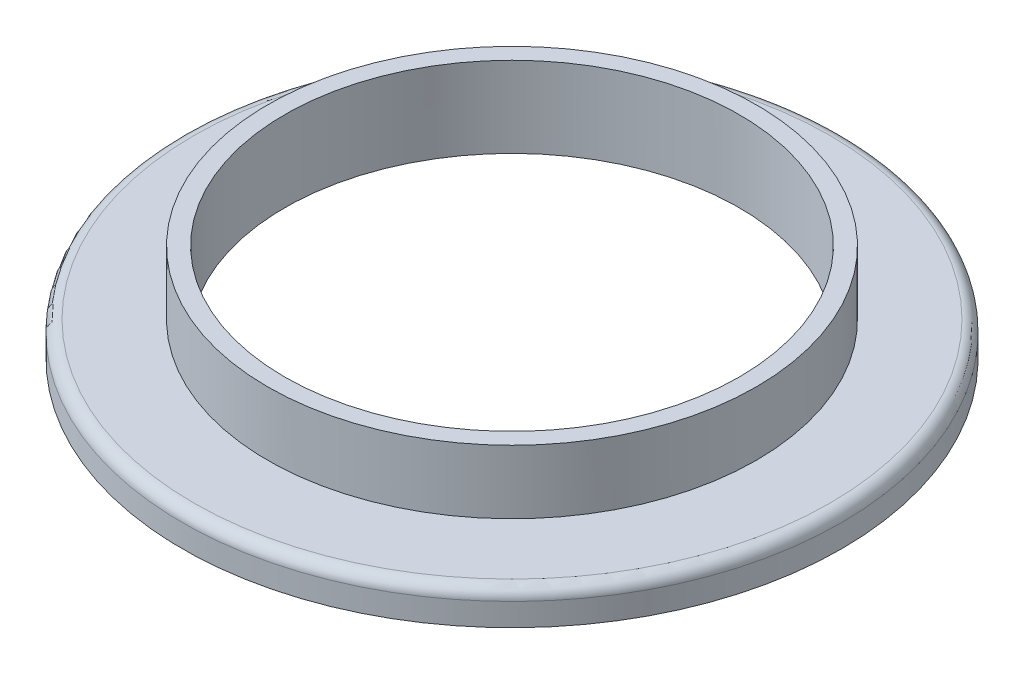
SolidWorks part; units mm, degrees
ref_plane "Front Plane" through (0, 0, 0) normal (0, 0, 1) x (1, 0, 0)
ref_plane "Top Plane" through (0, 0, 0) normal (0, 1, 0) x (1, 0, 0)
ref_plane "Right Plane" through (0, 0, 0) normal (1, 0, 0) x (0, 0, -1)
sketch "Sketch1" plane through (0, 0, 0) normal (0, 1, 0) x (1, 0, 0)
  circle A0 centre (0, 0) radius 20
  circle A1 centre (0, 0) radius 21.5
  dimension "D1" = 40
  dimension "D2" = 43
extrude "Boss-Extrude1" add sketch "Sketch1" along normal blind 10
sketch "Sketch3" plane through (0, 0, 0) normal (0, 0, 1) x (1, 0, 0)
  line L0 (21.5, 10) -> (-21.5, 10) construction
  line L1 (-27.2211, -5.0786) -> (24.7404, -5.0786)
  line L2 (-27.2211, -5.0786) -> (-27.2211, 2.9)
  line L3 (-27.2211, 2.9) -> (24.7404, 2.9)
  line L4 (24.7404, -5.0786) -> (24.7404, 2.9)
  dimension "D1" = 7.1
extrude "Cut-Extrude1" cut sketch "Sketch3" against normal blind 27 and the other way blind 24
sketch "Sketch4" plane through (0, 2.9, 0) normal (0, -1, 0) x (1, 0, 0)
  circle A0 centre (0, 0) radius 29
  circle A1 centre (0, 0) radius 21.5 construction
  circle A2 centre (0, 0) radius 20
  dimension "D1" = 7.5
extrude "Boss-Extrude2" add sketch "Sketch4" against normal blind 1.5 and the other way blind 1.5
sketch "Sketch6" plane through (0, 1.4, 0) normal (0, -1, 0) x (1, 0, 0)
  circle A0 centre (0, 0) radius 27.5
  circle A1 centre (0, 0) radius 29 construction
  dimension "D1" = 1.5
extrude "Cut-Extrude2" cut sketch "Sketch6" against normal blind 1.5
fillet "Fillet1" radius 1 2 edges at (29, 4.4, 0) (27.5, 2.9, 0)
